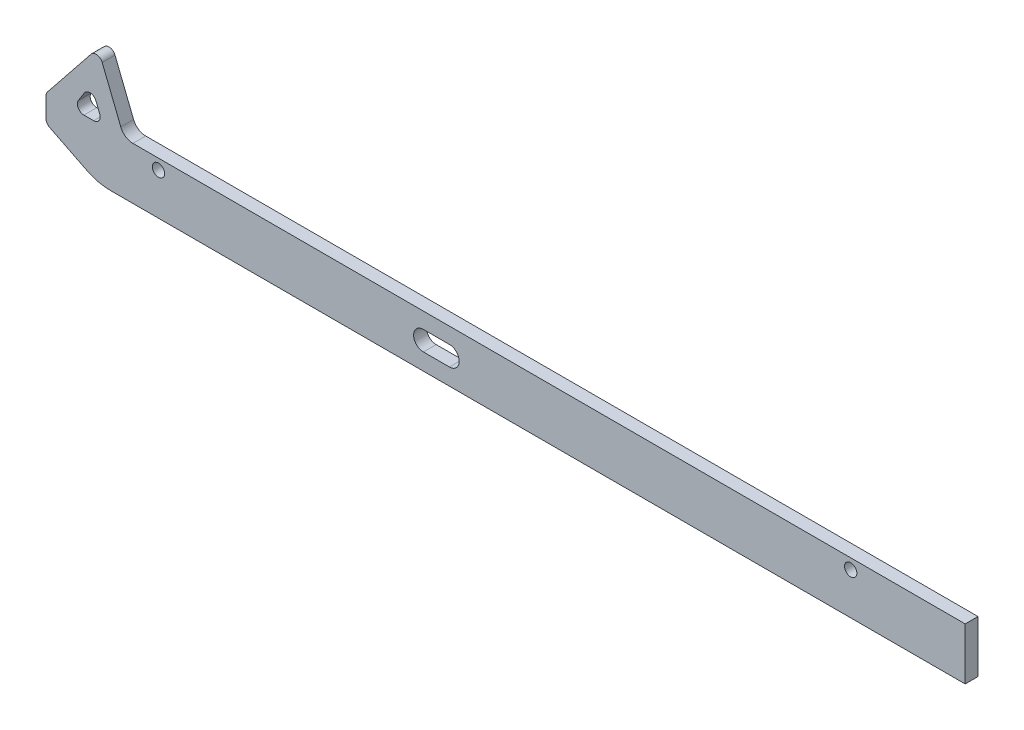
SolidWorks part; units mm, degrees
ref_plane "Front Plane" through (0, 0, 0) normal (0, 0, 1) x (1, 0, 0)
ref_plane "Top Plane" through (0, 0, 0) normal (0, 1, 0) x (1, 0, 0)
ref_plane "Right Plane" through (0, 0, 0) normal (1, 0, 0) x (0, 0, -1)
sketch "Sketch1" plane through (0, 0, 0) normal (0, 0, 1) x (1, 0, 0)
  line L0 (-110.4919, 6.2563) -> (-110.4919, 38.0063) construction
  line L1 (113.7998, -6.4437) -> (-97.7919, -6.4437)
  line L2 (113.7998, -6.4437) -> (113.7998, 6.2563)
  line L3 (113.7998, 6.2563) -> (-91.4419, 6.2563)
  line L4 (-97.7919, 22.1313) -> (-110.4919, 6.2563)
  line L5 (113.7998, -6.4437) -> (-110.4919, 6.2563) construction
  line L6 (113.7998, 6.2563) -> (-117.2068, -6.4437) construction
  line L7 (-110.4919, 38.0063) -> (-104.1419, 38.0063) construction
  line L8 (-110.4919, -0.0937) -> (-97.7919, -6.4437)
  line L9 (-104.1419, 38.0063) -> (-97.7919, 22.1313) construction
  line L10 (-104.1419, 6.2563) -> (-104.1419, 25.3063) construction
  line L11 (-104.1419, 25.3063) -> (-96.5219, 6.2563) construction
  line L12 (-104.1419, 6.2563) -> (-100.3319, 15.7813) construction
  line L13 (-100.3319, 15.7813) -> (-97.7919, 22.1313) construction
  line L14 (-110.4919, 6.2563) -> (-110.4919, -0.0937)
  line L15 (-97.7919, 22.1313) -> (-91.4419, 6.2563)
  line L16 (-104.1419, 6.2563) -> (-99.4608, 13.6034)
  line L17 (-99.4608, 13.6034) -> (-96.5219, 6.2563)
  line L18 (-96.5219, 6.2563) -> (-104.1419, 6.2563)
  line L19 (-97.7919, 22.1313) -> (-91.4419, 6.2563) construction
  point P0 (0, 0)
  dimension "D1" = 6.35
  dimension "D2" = 224.2918
  dimension "D3" = 6.35
  dimension "D4" = 12.7
  dimension "D5" = 31.75
  dimension "D6" = 19.05
  dimension "D7" = 6.35
  dimension "D9" = 12.7
extrude "Boss-Extrude1" add sketch "Sketch1" along normal blind 3.1242
fillet "Fillet4" radius 12.7 1 edges at (-97.7919, -6.4437, 1.5621)
fillet "Fillet8" radius 1.5875 6 edges at (-110.4919, -0.0937, 1.5621) (-110.4919, 6.2563, 1.5621) (-97.7919, 22.1313, 1.5621) (-99.4608, 13.6034, 1.5621) (-104.1419, 6.2563, 1.5621) (-96.5219, 6.2563, 1.5621)
fillet "Fillet9" radius 3.175 1 edges at (-91.4419, 6.2563, 1.5621)
sketch "Sketch2" plane through (0, 0, 3.1242) normal (0, 0, 1) x (1, 0, 0)
  line L0 (-18.4072, 0) -> (-12.0572, 0) construction
  line L1 (-18.4072, 2.3813) -> (-12.0572, 2.3813)
  line L2 (-18.4072, -2.3813) -> (-12.0572, -2.3813)
  line L4 (113.7998, -6.4437) -> (113.7998, 6.2563) construction
  arc A0 (-18.4072, 2.3813) -> (-18.4072, -2.3813) centre (-18.4072, 0) ccw
  arc A1 (-12.0572, -2.3813) -> (-12.0572, 2.3813) centre (-12.0572, 0) ccw
  point P3 (-15.2322, 0)
  point P8 (113.7998, -0.0937)
  dimension "D2" = 2.3813
  dimension "D1" = 6.35
  dimension "D3" = 129.032
extrude "Cut-Extrude1" cut sketch "Sketch2" against normal through all
sketch "Sketch3" plane through (0, 0, 3.1242) normal (0, 0, 1) x (1, 0, 0)
  line L0 (113.7998, 3.7163) -> (0, 3.7163) construction
  line L2 (-94.7939, -6.4437) -> (113.7998, -6.4437) construction
  line L3 (113.7998, -6.4437) -> (113.7998, 6.2563) construction
  circle A0 centre (85.8598, 3.7163) radius 1.5
  circle A1 centre (-83.0502, 3.7163) radius 1.5
  dimension "D1" = 3
  dimension "D4" = 3
  dimension "D2" = 27.94
  dimension "D3" = 10.16
  dimension "D5" = 196.85
extrude "Cut-Extrude2" cut sketch "Sketch3" against normal through all
